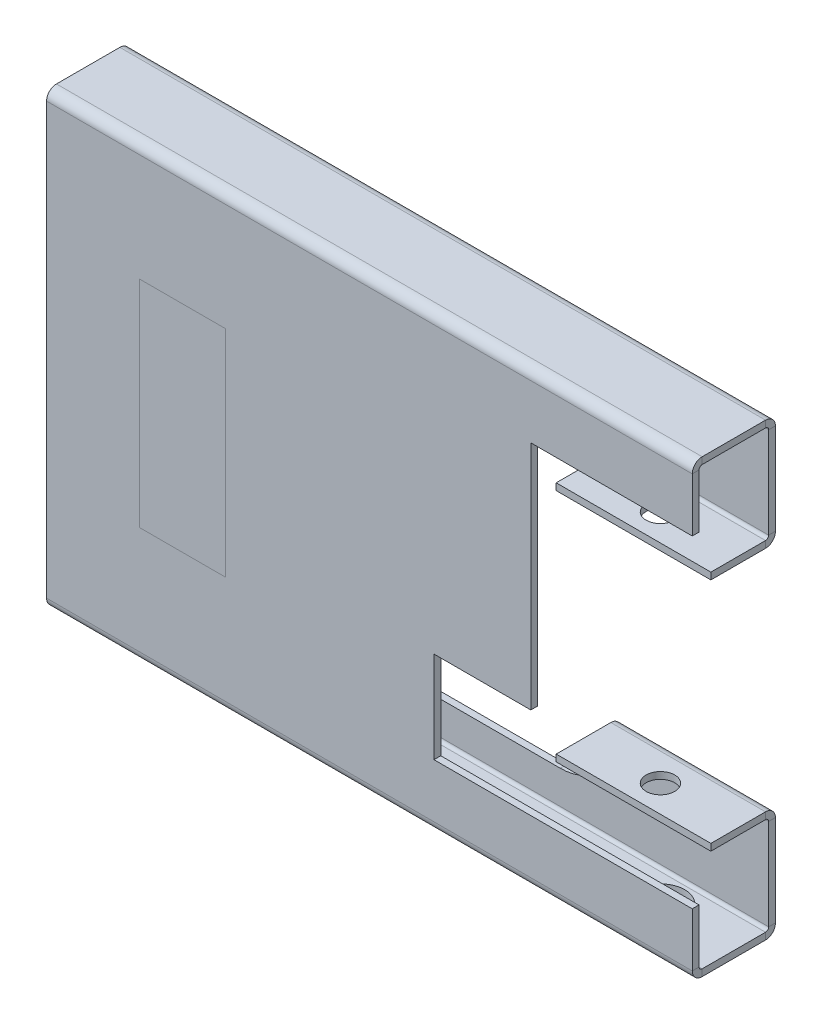
SolidWorks part; units mm, degrees
note: The reader was unsure of these and kept them because the rebuilt part matched: flange length of "Edge-Flange1", "Edge-Flange2", "Edge-Flange7", "Edge-Flange8", "Edge-Flange9", "Edge-Flange10".
material "5052-H32"
ref_plane "X-Y Datum" through (0, 0, 0) normal (0, 0, 1) x (1, 0, 0)
ref_plane "X-Z Datum" through (0, 0, 0) normal (0, 1, 0) x (1, 0, 0)
ref_plane "Y-Z Datum" through (0, 0, 0) normal (1, 0, 0) x (0, 0, -1)
sketch "Sketch1" plane through (0, 0, 0) normal (0, 0, 1) x (1, 0, 0)
  line L1 (76.2, 50.8) -> (-76.2, 50.8)
  line L3 (76.2, -50.8) -> (-76.2, -50.8)
  line L4 (-76.2, 50.8) -> (-76.2, -50.8)
  line L5 (76.2, 50.8) -> (-76.2, -50.8) construction
  line L6 (76.2, -50.8) -> (-76.2, 50.8) construction
  line L13 (76.2, 50.8) -> (76.2, -50.8)
  point P0 (0, 0)
  dimension "D6" = 101.6
  dimension "D8" = 152.4
base flange "Base-Flange1" sketch "Sketch1" thickness 1.6002 reverse thickness direction no parameters "D1"=0.7366
edge flange "Edge-Flange1" sketch "Sketch10" flange angle 90 flange length 19.6342 flange position bend outside bend radius 0.7366 thickness 1.6002 relief rectangular parameters "D6"=10
sketch "Sketch10" plane through (0, 50.8, -1.6002) normal (0, -1, 0) x (-1, 0, 0)
  line L2 (-76.2, 0) -> (-76.2, 18.034)
  line L3 (-76.2, 18.034) -> (76.2, 18.034)
  line L4 (76.2, 18.034) -> (76.2, 0)
  line L21 (76.2, 0) -> (-76.2, 0) construction
  line L22 (76.2, 0) -> (-76.2, 0)
bend "EdgeBend1" bend radius 0.7366 bend angle 90 parameters "D5"=2
edge flange "Edge-Flange2" sketch "Sketch13" flange angle 90 flange length 19.6342 flange position bend outside bend radius 0.7366 thickness 1.6002 relief rectangular parameters "D6"=10
sketch "Sketch13" plane through (0, -50.8, -1.6002) normal (0, 1, 0) x (1, 0, 0)
  line L2 (-76.2, 0) -> (-76.2, 18.034)
  line L3 (-76.2, 18.034) -> (76.2, 18.034)
  line L4 (76.2, 18.034) -> (76.2, 0)
  line L9 (76.2, 0) -> (-76.2, 0) construction
  line L10 (76.2, 0) -> (-76.2, 0)
bend "EdgeBend2" bend radius 0.7366 bend angle 90 parameters "D5"=3
sketch "Sketch14" plane through (0, 0, 0) normal (0, 0, 1) x (1, 0, 0)
  line L0 (76.2, -50.8) -> (76.2, 50.8) construction
  line L1 (76.2, 38.1) -> (15.24, 38.1)
  line L2 (76.2, 38.1) -> (76.2, -38.1)
  line L3 (76.2, -38.1) -> (15.24, -38.1)
  line L4 (15.24, 38.1) -> (15.24, -38.1)
  line L5 (38.1, -16.51) -> (38.1, 38.1)
  line L7 (38.1, -16.51) -> (15.24, -16.51)
  point P6 (15.24, 0)
  dimension "D1" = 76.2
  dimension "D2" = 60.96
  dimension "D3" = 38.1
  dimension "D5" = 21.59
extrude "Cut-Extrude1" cut sketch "Sketch14" against normal through all
ref_point "Point2"
edge flange "Edge-Flange7" sketch "Sketch31" flange angle 90 flange length 10.16 flange position material inside bend radius 0.7366 thickness 1.6002 relief rectangular parameters "D6"=10
sketch "Sketch31" plane through (0, -51.5366, -19.6342) normal (0, 0, -1) x (-1, 0, 0)
  line L2 (-76.2, 0) -> (-76.2, 8.5598)
  line L3 (-76.2, 8.5598) -> (76.2, 8.5598)
  line L4 (76.2, 8.5598) -> (76.2, 0)
  line L7 (-76.2, 0) -> (76.2, 0) construction
  line L8 (-76.2, 0) -> (76.2, 0)
bend "EdgeBend7" bend radius 0.7366 bend angle 90 parameters "D5"=8
edge flange "Edge-Flange8" sketch "Sketch34" flange angle 90 flange length 10.16 flange position material inside bend radius 0.7366 thickness 1.6002 relief rectangular parameters "D6"=10
sketch "Sketch34" plane through (0, 51.5366, -19.6342) normal (0, 0, -1) x (1, 0, 0)
  line L0 (-76.2, 0) -> (76.2, 0) construction
  line L1 (-76.2, 0) -> (76.2, 0)
  line L2 (-76.2, 0) -> (-76.2, 8.5598)
  line L3 (-76.2, 8.5598) -> (76.2, 8.5598)
  line L4 (76.2, 8.5598) -> (76.2, 0)
bend "EdgeBend8" bend radius 0.7366 bend angle 90 parameters "D5"=9
sketch "Sketch35" plane through (0, -42.9768, 0) normal (0, 1, 0) x (1, 0, 0)
  line L0 (-76.2, 18.034) -> (76.2, 18.034) construction
  line L1 (76.2, 19.6342) -> (39.69, 19.6342)
  line L2 (76.2, 19.6342) -> (76.2, 18.034)
  line L3 (76.2, 18.034) -> (39.69, 18.034)
  line L4 (39.69, 19.6342) -> (39.69, 18.034)
  dimension "D1" = 36.51
extrude "Boss-Extrude1" add sketch "Sketch35" along normal blind 16.0528
edge flange "Edge-Flange9" sketch "Sketch38" flange angle 90 flange length 15.24 flange position material inside bend radius 0.7366 thickness 1.6002 relief rectangular parameters "D6"=10
sketch "Sketch38" plane through (0, -26.924, -18.034) normal (0, 1, 0) x (-1, 0, 0)
  line L0 (-76.2, 0) -> (-39.69, 0) construction
  line L1 (-76.2, 0) -> (-39.69, 0)
  line L2 (-76.2, 0) -> (-76.2, 13.6398)
  line L3 (-76.2, 13.6398) -> (-39.69, 13.6398)
  line L4 (-39.69, 13.6398) -> (-39.69, 0)
bend "EdgeBend9" bend radius 0.7366 bend angle 90 parameters "D5"=10
sketch "Sketch39" plane through (0, 42.9768, 0) normal (0, -1, 0) x (1, 0, 0)
  line L0 (76.2, -19.6342) -> (-76.2, -19.6342) construction
  line L1 (76.2, -18.034) -> (39.69, -18.034)
  line L2 (76.2, -18.034) -> (76.2, -19.6342)
  line L3 (76.2, -19.6342) -> (39.69, -19.6342)
  line L4 (39.69, -18.034) -> (39.69, -19.6342)
  dimension "D1" = 36.51
extrude "Boss-Extrude2" add sketch "Sketch39" along normal blind 16.0528
edge flange "Edge-Flange10" sketch "Sketch42" flange angle 90 flange length 15.24 flange position material inside bend radius 0.7366 thickness 1.6002 relief rectangular parameters "D6"=10
sketch "Sketch42" plane through (0, 26.924, -18.034) normal (0, -1, 0) x (1, 0, 0)
  line L2 (39.69, 0) -> (39.69, 13.6398)
  line L3 (39.69, 13.6398) -> (76.2, 13.6398)
  line L4 (76.2, 13.6398) -> (76.2, 0)
  line L7 (39.69, 0) -> (76.2, 0) construction
  line L8 (39.69, 0) -> (76.2, 0)
bend "EdgeBend10" bend radius 0.7366 bend angle 90 parameters "D5"=11
sketch "Sketch43" plane through (0, -26.924, 0) normal (0, 1, 0) x (1, 0, 0)
  line L0 (76.2, 4.3942) -> (76.2, 17.2974) construction
  line L1 (39.69, 19.6342) -> (76.2, 19.6342) construction
  circle A0 centre (57.945, 10.7442) radius 3.3731
  dimension "D1" = 18.255
  dimension "D2" = 8.89
  dimension "D3" = 6.7462
extrude "Cut-Extrude2" cut sketch "Sketch43" against normal up to surface and the other way up to surface normal cut yes up to face at (57.945, -28.5242, -10.8458) other way up to face at (57.945, 28.5242, -10.8458)
fillet "Fillet1" radius 12.7 2 edges at (39.69, -42.9768, -18.8341) (39.69, 42.9768, -18.8341)
sketch "Sketch44" plane through (0, 0, 0) normal (0, 0, 1) x (1, 0, 0)
  line L1 (-54.2507, 25.4) -> (-33.9307, 25.4)
  line L2 (-54.2507, 25.4) -> (-54.2507, -25.4)
  line L3 (-54.2507, -25.4) -> (-33.9307, -25.4)
  line L4 (-33.9307, 25.4) -> (-33.9307, -25.4)
  point P4 (-33.9307, 0)
  dimension "D1" = 20.32
  dimension "D2" = 50.8
split line "Split Line1"
sketch "Sketch46" plane through (0, -53.1368, 0) normal (0, -1, 0) x (1, 0, 0)
  line L0 (76.2, -2.3368) -> (76.2, -17.2974) construction
  line L1 (-76.2, -19.6342) -> (76.2, -19.6342) construction
  circle A0 centre (57.945, -10.7442) radius 5.715
  dimension "D1" = 18.255
  dimension "D3" = 11.43
  dimension "D2" = 8.89
extrude "Cut-Extrude3" cut sketch "Sketch46" against normal up to next normal cut yes
sketch "Bend-Lines1" [suppressed] plane through (0, 0, 0) normal (0, 1, 0) x (1, 0, 0)
sketch "Bounding-Box1" [suppressed] plane through (0, 0, 0) normal (0, 1, 0) x (1, 0, 0)
sheet metal parameters "Sheet-Metal1" thickness 1.6002 parameters "D1"=0.7366
flat pattern "Flat-Pattern1" [suppressed]
sketch "Bend-Lines2" plane through (0, 0, 0) normal (0, 0, 1) x (1, 0, 0)
  line L0 (-76.2, -51.2703) -> (76.2, -51.2703) construction
  line L1 (-76.2, -51.2703) -> (76.2, -51.2703) construction
sketch3d "Bounding-Box2" [suppressed]
  line L0 (-76.2, -70.1802, 0) -> (76.2, -70.1802, 0) construction
  line L1 (-76.2, 70.1802, 0) -> (76.2, 70.1802, 0) construction
  line L2 (-76.2, -70.1802, 0) -> (-76.2, 70.1802, 0) construction
  line L3 (76.2, -70.1802, 0) -> (76.2, 70.1802, 0) construction
sheet metal parameters "Sheet-Metal2" thickness 1.6002 parameters "D1"=0.7366
flat pattern "Flat-Pattern1"
sketch "Bend-Lines2" plane through (0, 0, 0) normal (0, 0, 1) x (1, 0, 0)
  line L2 (76.2, 52.0069) -> (-76.2, 52.0069) construction
  line L3 (76.2, 52.0069) -> (-76.2, 52.0069) construction
sketch3d "Bounding-Box2" [suppressed]
  line L0 (-76.2, -50.8, 0) -> (76.2, -50.8, 0) construction
  line L1 (-76.2, 71.8574, 0) -> (76.2, 71.8574, 0) construction
  line L2 (-76.2, -50.8, 0) -> (-76.2, 71.8574, 0) construction
  line L3 (76.2, -50.8, 0) -> (76.2, 71.8574, 0) construction
bend of the flat pattern "Flatten-<EdgeBend1>1"
sheet metal parameters "Sheet-Metal3" thickness 1.6002 parameters "D1"=0.7366
flat pattern "Flat-Pattern1"
sketch "Bend-Lines2" plane through (0, 0, 0) normal (0, 0, 1) x (1, 0, 0)
  line L0 (-76.2, -52.0069) -> (76.2, -52.0069) construction
  line L1 (-76.2, -52.0069) -> (76.2, -52.0069) construction
  line L2 (76.2, 52.0069) -> (-76.2, 52.0069) construction
  line L3 (76.2, 52.0069) -> (-76.2, 52.0069) construction
sketch3d "Bounding-Box2" [suppressed]
  line L0 (-76.2, -71.8574, 0) -> (76.2, -71.8574, 0) construction
  line L1 (-76.2, 71.8574, 0) -> (76.2, 71.8574, 0) construction
  line L2 (-76.2, -71.8574, 0) -> (-76.2, 71.8574, 0) construction
  line L3 (76.2, -71.8574, 0) -> (76.2, 71.8574, 0) construction
bend of the flat pattern "Flatten-<EdgeBend1>1"
bend of the flat pattern "Flatten-<EdgeBend2>1"
sheet metal parameters "Sheet-Metal4" thickness 1.6002 parameters "D1"=0.7366
flat pattern "Flat-Pattern1"
sketch "Bend-Lines2" plane through (0, 0, 0) normal (0, 0, 1) x (1, 0, 0)
  line L0 (-76.2, -52.0069) -> (76.2, -52.0069) construction
  line L1 (-76.2, -52.0069) -> (76.2, -52.0069) construction
  line L2 (76.2, 52.0069) -> (-76.2, 52.0069) construction
  line L3 (76.2, 52.0069) -> (-76.2, 52.0069) construction
sketch3d "Bounding-Box2" [suppressed]
  line L0 (-76.2, -71.8574, 0) -> (76.2, -71.8574, 0) construction
  line L1 (-76.2, 71.8574, 0) -> (76.2, 71.8574, 0) construction
  line L2 (-76.2, -71.8574, 0) -> (-76.2, 71.8574, 0) construction
  line L3 (76.2, -71.8574, 0) -> (76.2, 71.8574, 0) construction
bend of the flat pattern "Flatten-<EdgeBend1>1"
bend of the flat pattern "Flatten-<EdgeBend2>1"
sheet metal parameters "Sheet-Metal16" thickness 1.6002 parameters "D1"=0.7366
flat pattern "Flat-Pattern1"
sketch "Bend-Lines2" plane through (0, 0, 0) normal (0, 0, 1) x (1, 0, 0)
  line L0 (-76.2, -52.0069) -> (76.2, -52.0069) construction
  line L1 (-76.2, -52.0069) -> (76.2, -52.0069) construction
  line L2 (76.2, 52.0069) -> (-76.2, 52.0069) construction
  line L3 (76.2, 52.0069) -> (-76.2, 52.0069) construction
  line L4 (76.2, -24.3709) -> (39.69, -24.3709) construction
  line L5 (76.2, -24.3709) -> (39.69, -24.3709) construction
  line L6 (39.69, 24.3709) -> (76.2, 24.3709) construction
  line L7 (39.69, 24.3709) -> (76.2, 24.3709) construction
  line L8 (76.2, -6.9964) -> (39.69, -6.9964) construction
  line L9 (76.2, -6.9964) -> (39.69, -6.9964) construction
  line L10 (39.69, 6.9964) -> (76.2, 6.9964) construction
  line L11 (39.69, 6.9964) -> (76.2, 6.9964) construction
  line L12 (-76.2, -69.3814) -> (76.2, -69.3814) construction
  line L13 (-76.2, -69.3814) -> (76.2, -69.3814) construction
sketch3d "Bounding-Box2" [suppressed]
  line L0 (-76.2, -78.4115, 0) -> (76.2, -78.4115, 0) construction
  line L1 (-76.2, 70.5112, 0) -> (76.2, 70.5112, 0) construction
  line L2 (-76.2, -78.4115, 0) -> (-76.2, 70.5112, 0) construction
  line L3 (76.2, -78.4115, 0) -> (76.2, 70.5112, 0) construction
bend of the flat pattern "Flatten-<EdgeBend1>1"
bend of the flat pattern "Flatten-<EdgeBend2>1"
bend of the flat pattern "Flatten-<EdgeBend7>1"
sheet metal parameters "Sheet-Metal17" thickness 1.6002 parameters "D1"=0.7366
flat pattern "Flat-Pattern1"
sketch "Bend-Lines2" plane through (0, 0, 0) normal (0, 0, 1) x (1, 0, 0)
  line L0 (-76.2, -52.2762) -> (76.2, -52.2762) construction
  line L1 (-76.2, -52.2762) -> (76.2, -52.2762) construction
  line L2 (76.2, 52.2762) -> (-76.2, 52.2762) construction
  line L3 (76.2, 52.2762) -> (-76.2, 52.2762) construction
  line L12 (-76.2, -68.8177) -> (76.2, -68.8177) construction
  line L13 (-76.2, -68.8177) -> (76.2, -68.8177) construction
  line L14 (76.2, 68.8177) -> (-76.2, 68.8177) construction
  line L15 (76.2, 68.8177) -> (-76.2, 68.8177) construction
  point P4 (76.2, -24.7874)
  point P5 (39.69, -24.7874)
  point P6 (39.69, 24.7874)
  point P7 (76.2, 24.7874)
  point P8 (76.2, -8.2459)
  point P9 (39.69, -8.2459)
  point P10 (39.69, 8.2459)
  point P11 (76.2, 8.2459)
sketch3d "Bounding-Box2" [suppressed]
  line L0 (76.2, 77.4313, 0) -> (76.2, -77.4313, 0) construction
  line L1 (-76.2, 77.4313, 0) -> (-76.2, -77.4313, 0) construction
  line L2 (76.2, 77.4313, 0) -> (-76.2, 77.4313, 0) construction
  line L3 (76.2, -77.4313, 0) -> (-76.2, -77.4313, 0) construction
bend of the flat pattern "Flatten-<EdgeBend1>1"
bend of the flat pattern "Flatten-<EdgeBend2>1"
bend of the flat pattern "Flatten-<EdgeBend7>1"
bend of the flat pattern "Flatten-<EdgeBend8>1"
sheet metal parameters "Sheet-Metal50" thickness 1.6002 parameters "D1"=0.7366
flat pattern "Flat-Pattern1"
sketch "Bend-Lines2" plane through (0, 0, 0) normal (0, 0, 1) x (1, 0, 0)
  line L0 (-76.2, -52.2762) -> (76.2, -52.2762) construction
  line L1 (-76.2, -52.2762) -> (76.2, -52.2762) construction
  line L2 (76.2, 52.2762) -> (-76.2, 52.2762) construction
  line L3 (76.2, 52.2762) -> (-76.2, 52.2762) construction
  line L12 (-76.2, -68.8177) -> (76.2, -68.8177) construction
  line L13 (-76.2, -68.8177) -> (76.2, -68.8177) construction
  line L14 (76.2, 68.8177) -> (-76.2, 68.8177) construction
  line L15 (76.2, 68.8177) -> (-76.2, 68.8177) construction
sketch3d "Bounding-Box2" [suppressed]
  line L0 (76.2, 77.4313, 0) -> (76.2, -97.8529, 0) construction
  line L1 (-76.2, 77.4313, 0) -> (-76.2, -97.8529, 0) construction
  line L2 (76.2, 77.4313, 0) -> (-76.2, 77.4313, 0) construction
  line L3 (76.2, -97.8529, 0) -> (-76.2, -97.8529, 0) construction
bend of the flat pattern "Flatten-<EdgeBend1>1"
bend of the flat pattern "Flatten-<EdgeBend2>1"
bend of the flat pattern "Flatten-<EdgeBend7>1"
bend of the flat pattern "Flatten-<EdgeBend8>1"
sheet metal parameters "Sheet-Metal51" thickness 1.6002 parameters "D1"=0.7366
flat pattern "Flat-Pattern1"
sketch "Bend-Lines2" plane through (0, 0, 0) normal (0, 0, 1) x (1, 0, 0)
  line L0 (-76.2, -52.2762) -> (76.2, -52.2762) construction
  line L1 (-76.2, -52.2762) -> (76.2, -52.2762) construction
  line L2 (76.2, 52.2762) -> (-76.2, 52.2762) construction
  line L3 (76.2, 52.2762) -> (-76.2, 52.2762) construction
  line L4 (39.69, -96.3066) -> (76.2, -96.3066) construction
  line L5 (39.69, -96.3066) -> (76.2, -96.3066) construction
  line L12 (-76.2, -68.8177) -> (76.2, -68.8177) construction
  line L13 (-76.2, -68.8177) -> (76.2, -68.8177) construction
  line L14 (76.2, 68.8177) -> (-76.2, 68.8177) construction
  line L15 (76.2, 68.8177) -> (-76.2, 68.8177) construction
sketch3d "Bounding-Box2" [suppressed]
  line L0 (76.2, 77.4313, 0) -> (76.2, -110.0002, 0) construction
  line L1 (-76.2, 77.4313, 0) -> (-76.2, -110.0002, 0) construction
  line L2 (76.2, 77.4313, 0) -> (-76.2, 77.4313, 0) construction
  line L3 (76.2, -110.0002, 0) -> (-76.2, -110.0002, 0) construction
bend of the flat pattern "Flatten-<EdgeBend1>1"
bend of the flat pattern "Flatten-<EdgeBend2>1"
bend of the flat pattern "Flatten-<EdgeBend7>1"
bend of the flat pattern "Flatten-<EdgeBend8>1"
bend of the flat pattern "Flatten-<EdgeBend9>1"
sheet metal parameters "Sheet-Metal53" thickness 1.6002 parameters "D1"=0.7366
flat pattern "Flat-Pattern1"
sketch "Bend-Lines2" plane through (0, 0, 0) normal (0, 0, 1) x (1, 0, 0)
  line L0 (-76.2, -52.2762) -> (76.2, -52.2762) construction
  line L1 (-76.2, -52.2762) -> (76.2, -52.2762) construction
  line L2 (76.2, 52.2762) -> (-76.2, 52.2762) construction
  line L3 (76.2, 52.2762) -> (-76.2, 52.2762) construction
  line L4 (39.69, -96.3066) -> (76.2, -96.3066) construction
  line L5 (39.69, -96.3066) -> (76.2, -96.3066) construction
  line L12 (-76.2, -68.8177) -> (76.2, -68.8177) construction
  line L13 (-76.2, -68.8177) -> (76.2, -68.8177) construction
  line L14 (76.2, 68.8177) -> (-76.2, 68.8177) construction
  line L15 (76.2, 68.8177) -> (-76.2, 68.8177) construction
sketch3d "Bounding-Box2" [suppressed]
  line L0 (76.2, 97.8529, 0) -> (76.2, -110.0002, 0) construction
  line L1 (-76.2, 97.8529, 0) -> (-76.2, -110.0002, 0) construction
  line L2 (76.2, 97.8529, 0) -> (-76.2, 97.8529, 0) construction
  line L3 (76.2, -110.0002, 0) -> (-76.2, -110.0002, 0) construction
bend of the flat pattern "Flatten-<EdgeBend1>1"
bend of the flat pattern "Flatten-<EdgeBend2>1"
bend of the flat pattern "Flatten-<EdgeBend7>1"
bend of the flat pattern "Flatten-<EdgeBend8>1"
bend of the flat pattern "Flatten-<EdgeBend9>1"
sheet metal parameters "Sheet-Metal54" thickness 1.6002 parameters "D1"=0.7366
flat pattern "Flat-Pattern1"
sketch "Bend-Lines2" plane through (0, 0, 0) normal (0, 0, 1) x (1, 0, 0)
  line L0 (-76.2, -52.2762) -> (76.2, -52.2762) construction
  line L1 (-76.2, -52.2762) -> (76.2, -52.2762) construction
  line L2 (76.2, 52.2762) -> (-76.2, 52.2762) construction
  line L3 (76.2, 52.2762) -> (-76.2, 52.2762) construction
  line L4 (39.69, -96.3066) -> (76.2, -96.3066) construction
  line L5 (39.69, -96.3066) -> (76.2, -96.3066) construction
  line L6 (76.2, 96.3066) -> (39.69, 96.3066) construction
  line L7 (76.2, 96.3066) -> (39.69, 96.3066) construction
  line L12 (-76.2, -68.8177) -> (76.2, -68.8177) construction
  line L13 (-76.2, -68.8177) -> (76.2, -68.8177) construction
  line L14 (76.2, 68.8177) -> (-76.2, 68.8177) construction
  line L15 (76.2, 68.8177) -> (-76.2, 68.8177) construction
sketch3d "Bounding-Box2" [suppressed]
  line L0 (76.2, 110.0002, 0) -> (76.2, -110.0002, 0) construction
  line L1 (-76.2, 110.0002, 0) -> (-76.2, -110.0002, 0) construction
  line L2 (76.2, 110.0002, 0) -> (-76.2, 110.0002, 0) construction
  line L3 (76.2, -110.0002, 0) -> (-76.2, -110.0002, 0) construction
bend of the flat pattern "Flatten-<EdgeBend1>1"
bend of the flat pattern "Flatten-<EdgeBend2>1"
bend of the flat pattern "Flatten-<EdgeBend7>1"
bend of the flat pattern "Flatten-<EdgeBend8>1"
bend of the flat pattern "Flatten-<EdgeBend9>1"
bend of the flat pattern "Flatten-<EdgeBend10>1"
sheet metal parameters "Sheet-Metal55" thickness 1.6002 parameters "D1"=0.7366
flat pattern "Flat-Pattern1"
sketch "Bend-Lines2" plane through (0, 0, 0) normal (0, 0, 1) x (1, 0, 0)
  line L0 (-76.2, -52.0069) -> (76.2, -52.0069) construction
  line L1 (-76.2, -52.0069) -> (76.2, -52.0069) construction
  line L2 (76.2, 52.0069) -> (-76.2, 52.0069) construction
  line L3 (76.2, 52.0069) -> (-76.2, 52.0069) construction
  line L4 (39.69, -97.0174) -> (76.2, -97.0174) construction
  line L5 (39.69, -97.0174) -> (76.2, -97.0174) construction
  line L6 (76.2, 97.0174) -> (39.69, 97.0174) construction
  line L7 (76.2, 97.0174) -> (39.69, 97.0174) construction
  line L12 (-76.2, -69.3814) -> (76.2, -69.3814) construction
  line L13 (-76.2, -69.3814) -> (76.2, -69.3814) construction
  line L14 (76.2, 69.3814) -> (-76.2, 69.3814) construction
  line L15 (76.2, 69.3814) -> (-76.2, 69.3814) construction
sketch3d "Bounding-Box2" [suppressed]
  line L0 (76.2, 111.1275, 0) -> (76.2, -111.1275, 0) construction
  line L1 (-76.2, 111.1275, 0) -> (-76.2, -111.1275, 0) construction
  line L2 (76.2, 111.1275, 0) -> (-76.2, 111.1275, 0) construction
  line L3 (76.2, -111.1275, 0) -> (-76.2, -111.1275, 0) construction
bend of the flat pattern "Flatten-<EdgeBend1>1"
bend of the flat pattern "Flatten-<EdgeBend2>1"
bend of the flat pattern "Flatten-<EdgeBend7>1"
bend of the flat pattern "Flatten-<EdgeBend8>1"
bend of the flat pattern "Flatten-<EdgeBend9>1"
bend of the flat pattern "Flatten-<EdgeBend10>1"
sheet metal parameters "Sheet-Metal63" thickness 1.6002 parameters "D1"=0.7366
flat pattern "Flat-Pattern1" [suppressed]
sketch "Bend-Lines2" plane through (0, 0, -1.6002) normal (0, 0, -1) x (-1, 0, 0)
  line L0 (76.2, -52.0069) -> (-76.2, -52.0069) construction
  line L1 (76.2, -52.0069) -> (-76.2, -52.0069) construction
  line L2 (-76.2, 52.0069) -> (76.2, 52.0069) construction
  line L3 (-76.2, 52.0069) -> (76.2, 52.0069) construction
  line L4 (-39.69, -93.3344) -> (-76.2, -93.3344) construction
  line L5 (-39.69, -93.3344) -> (-76.2, -93.3344) construction
  line L6 (-76.2, 93.3344) -> (-39.69, 93.3344) construction
  line L7 (-76.2, 93.3344) -> (-39.69, 93.3344) construction
  line L12 (76.2, -69.3814) -> (-76.2, -69.3814) construction
  line L13 (76.2, -69.3814) -> (-76.2, -69.3814) construction
  line L14 (-76.2, 69.3814) -> (76.2, 69.3814) construction
  line L15 (-76.2, 69.3814) -> (76.2, 69.3814) construction
sketch3d "Bounding-Box2" [suppressed]
  line L0 (-76.2, 107.4445, 0) -> (-76.2, -107.4445, 0) construction
  line L1 (76.2, 107.4445, 0) -> (76.2, -107.4445, 0) construction
  line L2 (-76.2, 107.4445, 0) -> (76.2, 107.4445, 0) construction
  line L3 (-76.2, -107.4445, 0) -> (76.2, -107.4445, 0) construction
bend of the flat pattern "Flatten-<EdgeBend1>1"
bend of the flat pattern "Flatten-<EdgeBend2>1"
bend of the flat pattern "Flatten-<EdgeBend7>1"
bend of the flat pattern "Flatten-<EdgeBend8>1"
bend of the flat pattern "Flatten-<EdgeBend9>1"
bend of the flat pattern "Flatten-<EdgeBend10>1"
sketch "Sketch45-1" [suppressed] plane through (0, 50.877, 0) normal (0, 0, 1) x (1, 0, 0)
  line L0 (76.2, 19.6342) -> (-76.2, 19.6342) construction
  line L1 (76.2, 56.5675) -> (76.2, -12.777) construction
  circle A0 centre (57.945, 10.7442) radius 5.715
  dimension "D1" = 11.43
  dimension "D2" = 8.89
  dimension "D3" = 18.255
sketch "Sketch46-1" [suppressed] plane through (0, -50.877, 0) normal (0, 0, 1) x (1, 0, 0)
  line L0 (76.2, 12.777) -> (76.2, -56.5675) construction
  line L1 (-76.2, -19.6342) -> (76.2, -19.6342) construction
  circle A0 centre (57.945, -10.7442) radius 5.715
  dimension "D1" = 18.255
  dimension "D3" = 11.43
  dimension "D2" = 8.89
sheet metal parameters "Sheet-Metal70" thickness 1.6002 parameters "D1"=0.7366
flat pattern "Flat-Pattern1" [suppressed]
sketch "Bend-Lines2" plane through (0, 0, -1.6002) normal (0, 0, -1) x (-1, 0, 0)
  line L0 (76.2, -52.0069) -> (-76.2, -52.0069) construction
  line L1 (76.2, -52.0069) -> (-76.2, -52.0069) construction
  line L2 (-76.2, 52.0069) -> (76.2, 52.0069) construction
  line L3 (-76.2, 52.0069) -> (76.2, 52.0069) construction
  line L4 (-39.69, -93.3344) -> (-76.2, -93.3344) construction
  line L5 (-39.69, -93.3344) -> (-76.2, -93.3344) construction
  line L6 (-76.2, 93.3344) -> (-39.69, 93.3344) construction
  line L7 (-76.2, 93.3344) -> (-39.69, 93.3344) construction
  line L12 (76.2, -69.3814) -> (-76.2, -69.3814) construction
  line L13 (76.2, -69.3814) -> (-76.2, -69.3814) construction
  line L14 (-76.2, 69.3814) -> (76.2, 69.3814) construction
  line L15 (-76.2, 69.3814) -> (76.2, 69.3814) construction
sketch3d "Bounding-Box2" [suppressed]
  line L0 (-76.2, 107.4445, 0) -> (-76.2, -107.4445, 0) construction
  line L1 (76.2, 107.4445, 0) -> (76.2, -107.4445, 0) construction
  line L2 (-76.2, 107.4445, 0) -> (76.2, 107.4445, 0) construction
  line L3 (-76.2, -107.4445, 0) -> (76.2, -107.4445, 0) construction
bend of the flat pattern "Flatten-<EdgeBend1>1"
bend of the flat pattern "Flatten-<EdgeBend2>1"
bend of the flat pattern "Flatten-<EdgeBend7>1"
bend of the flat pattern "Flatten-<EdgeBend8>1"
bend of the flat pattern "Flatten-<EdgeBend9>1"
bend of the flat pattern "Flatten-<EdgeBend10>1"
sketch "Sketch46-1" plane through (0, -50.877, 0) normal (0, 0, 1) x (1, 0, 0)
  line L0 (76.2, 12.777) -> (76.2, -56.5675) construction
  line L1 (-76.2, -19.6342) -> (76.2, -19.6342) construction
  circle A0 centre (57.945, -10.7442) radius 5.715
  dimension "D1" = 18.255
  dimension "D3" = 11.43
  dimension "D2" = 8.89
equation "\"t\"= 0.063"
equation "\"D7@Edge-Flange1\"=0.7+.063in+.01"
equation "\"D7@Edge-Flange2\"=.7+.063+.01"
equation "\"D1@Boss-Extrude2\"=1.81in+.02"
equation "\"D1@Boss-Extrude1\"=1.81in+.02"
